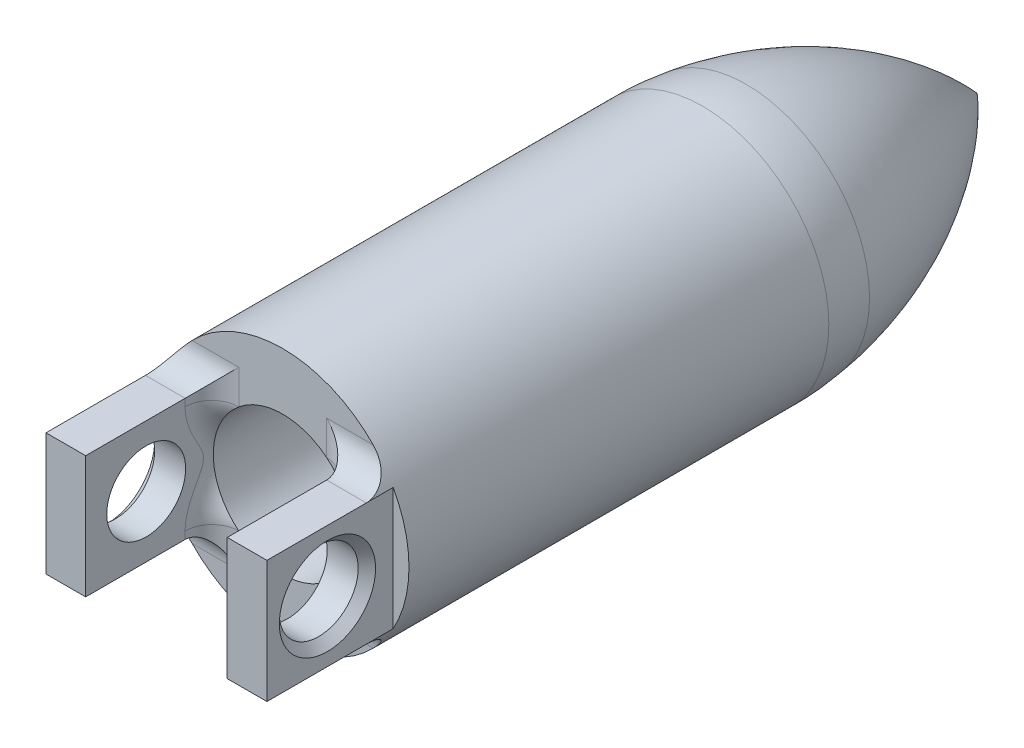
SolidWorks part; units mm, degrees
ref_plane "Front Plane" through (0, 0, 0) normal (0, 0, 1) x (1, 0, 0)
ref_plane "Top Plane" through (0, 0, 0) normal (0, 1, 0) x (1, 0, 0)
ref_plane "Right Plane" through (0, 0, 0) normal (1, 0, 0) x (0, 0, -1)
sketch "Sketch1" plane through (0, 0, 0) normal (0, 1, 0) x (1, 0, 0)
  line L0 (0, 0) -> (0, 22)
  line L1 (0, 0) -> (4, 0)
  line L2 (4, 0) -> (4, 13.7068)
  arc A0 (0, 22) -> (4, 13.7068) centre (-8.0282, 13.0165) cw
  dimension "D1" = 22
  dimension "D2" = 4
revolve "Revolve1" add sketch "Sketch1" angle 360 about L0
shell "Shell1" thickness 1.8 removed face at (4, 0, 0)
fillet "Fillet1" radius 10 1 edges at (4, 0, -13.7068)
sketch "Sketch9" plane through (0, 0, 0) normal (0, 0, 1) x (1, 0, 0)
  line L0 (0, 3.9166) -> (0, -4) construction
  line L1 (-2.2425, -1.9377) -> (-3.4994, -1.9377)
  line L2 (-2.2425, -1.9377) -> (-2.2425, 1.9377)
  line L3 (-2.2425, 1.9377) -> (-3.4994, 1.9377)
  line L4 (-3.4994, -1.9377) -> (-3.4994, 1.9377)
  line L5 (-2.2425, -1.9377) -> (-3.4994, 1.9377) construction
  line L6 (-2.2425, 1.9377) -> (-3.4994, -1.9377) construction
  line L7 (2.2425, -1.9377) -> (3.4994, -1.9377)
  line L8 (2.2425, -1.9377) -> (2.2425, 1.9377)
  line L9 (3.4994, -1.9377) -> (3.4994, 1.9377)
  line L10 (2.2425, 1.9377) -> (3.4994, 1.9377)
  circle A0 centre (0, 0) radius 4 construction
  point P0 (-2.8709, 0)
extrude "Boss-Extrude4" add sketch "Sketch9" along normal blind 4
hole_wizard "M3 Tapped Hole2" positions "Sketch10" profile "Sketch11" tap size "M3" standard "ISO"
sketch "Sketch10" plane through (3.4994, 0, 0) normal (1, 0, 0) x (0, 0, -1)
  point P0 (-2.0826, 0)
cosmetic thread "Hole Thread2" parameters "D2"=3
sketch "Sketch11" plane through (3.4994, 0, 2.0826) normal (0, 1, 0) x (0, 0, -1)
  line L0 (0, 0) -> (0, 2.9711)
  line L1 (0, 2.9711) -> (1.25, 2.22)
  line L2 (1.25, 2.22) -> (1.25, 0.275)
  line L3 (1.25, 0.275) -> (1.525, 0)
  line L5 (1.525, 0) -> (0, 0)
  line L6 (-1.25, 0.275) -> (-1.525, 0) construction
  line L10 (0, 2.9711) -> (-1.25, 2.22) construction
  line L11 (0, -6.35) -> (0, 107.95) construction
  dimension "Tap Drill Dia." = 2.5
  dimension "Tap Drill Depth" = 2.22
  dimension "Near C'Sink Dia." = 3.05
  dimension "Near C'Sink Angle" = 90
  dimension "Drill Angle" = 118
mirror "Mirror1" about plane through (0, 0, 0) normal (1, 0, 0) of "M3 Tapped Hole2"
cosmetic thread "Hole Thread4" parameters "D1"=6.72, "D2"=3
fillet "Fillet2" radius 0.85 6 edges at (-2.2425, 0, 0) (-2.8709, -1.9377, 0) (-2.8709, 1.9377, 0) (2.8709, 1.9377, 0) (2.8709, -1.9377, 0) (2.2425, 0, 0)
